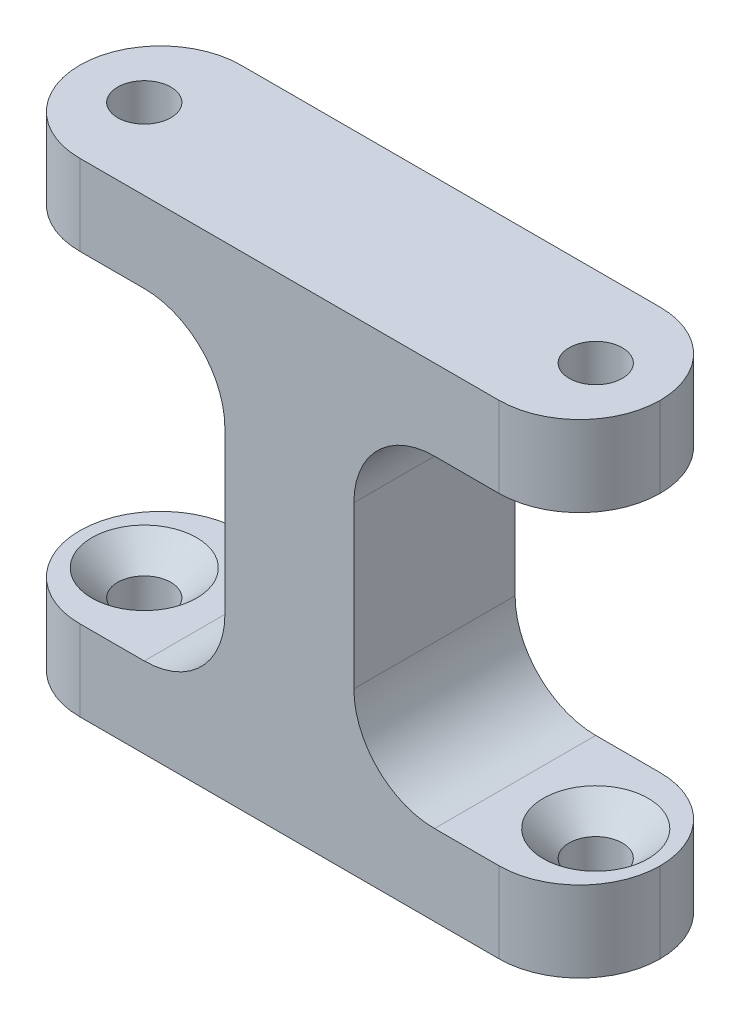
SolidWorks part; units mm, degrees
material "PLA Black"
ref_plane "Front Plane" through (0, 0, 0) normal (0, 0, 1) x (1, 0, 0)
ref_plane "Top Plane" through (0, 0, 0) normal (0, 1, 0) x (1, 0, 0)
ref_plane "Right Plane" through (0, 0, 0) normal (1, 0, 0) x (0, 0, -1)
sketch "Sketch1" plane through (0, 0, 0) normal (0, 0, 1) x (1, 0, 0)
  line L0 (0, 0) -> (0, 5)
  line L1 (0, 5) -> (-14, 5)
  line L2 (-14, 5) -> (-14, 25)
  line L3 (-14, 25) -> (0, 25)
  line L4 (0, 25) -> (0, 30)
  line L5 (0, 30) -> (-36, 30)
  line L6 (-36, 30) -> (-36, 25)
  line L7 (-36, 25) -> (-22, 25)
  line L8 (-22, 25) -> (-22, 5)
  line L9 (-22, 5) -> (-36, 5)
  line L10 (-36, 5) -> (-36, 0)
  line L11 (-36, 0) -> (0, 0)
  line L12 (-18, 30) -> (-18, 35.187) construction
  dimension "D1" = 36
  dimension "D2" = 30
  dimension "D3" = 5
  dimension "D4" = 5
  dimension "D6" = 4
  dimension "8" = 8
extrude "Boss-Extrude1" add sketch "Sketch1" along normal blind 10
sketch "Sketch2" plane through (0, 30, 0) normal (0, 1, 0) x (1, 0, 0)
  line L0 (0, 0) -> (-36, 0) construction
  line L2 (-18, 0) -> (-18, 9.2257) construction
  circle A0 centre (-32, -5) radius 1.65
  circle A1 centre (-4, -5) radius 1.65
  dimension "D1" = 3.3
  dimension "D2" = 3.3
  dimension "D3" = 28
  dimension "D4" = 5
  dimension "D5" = 14
extrude "Cut-Extrude1" cut sketch "Sketch2" against normal through all both and the other way through all
chamfer "Chamfer1" distance 1.6 angle 45 2 edges at (-30.35, 5, 5) (-2.35, 5, 5)
fillet "Fillet1" radius 5 4 edges at (-14, 25, 5) (-22, 25, 5) (-22, 5, 5) (-14, 5, 5)
fillet "Fillet2" radius 5 8 edges at (0, 27.5, 10) (0, 27.5, 0) (0, 2.5, 0) (0, 2.5, 10) (-36, 2.5, 0) (-36, 2.5, 10) (-36, 27.5, 0) (-36, 27.5, 10)
